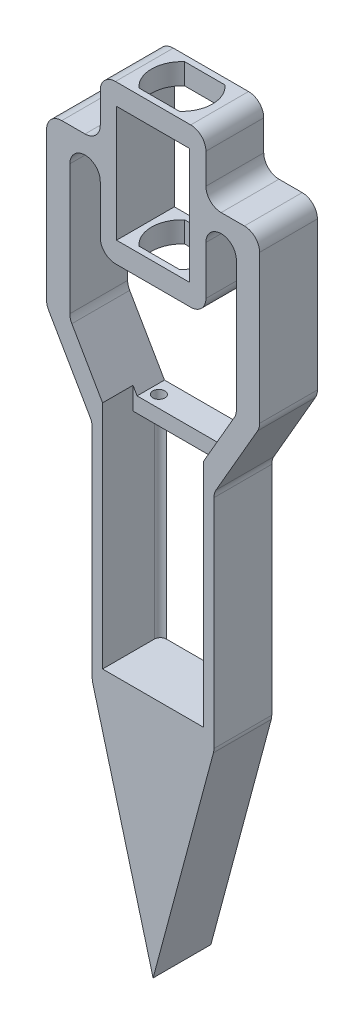
SolidWorks part; units mm, degrees
ref_plane "Front Plane" through (0, 0, 0) normal (0, 0, 1) x (1, 0, 0)
ref_plane "Top Plane" through (0, 0, 0) normal (0, 1, 0) x (1, 0, 0)
ref_plane "Right Plane" through (0, 0, 0) normal (1, 0, 0) x (0, 0, -1)
sketch "Sketch1" plane through (0, 0, 0) normal (0, 1, 0) x (1, 0, 0)
  line L0 (0, -7.5) -> (-6.64, -7.5)
  line L1 (-6.64, 7.5) -> (0, 7.5)
  line L2 (0, 7.5) -> (6.64, 7.5)
  line L3 (6.64, -7.5) -> (0, -7.5)
  line L4 (0.0497, 0) -> (-0.0497, 0) construction
  line L5 (0, -9.5) -> (-7.3633, -9.5)
  line L6 (-7.3633, 9.5) -> (0, 9.5)
  line L7 (0, 9.5) -> (7.3633, 9.5)
  line L8 (7.3633, -9.5) -> (0, -9.5)
  line L9 (0.0497, 2) -> (-0.0497, 2)
  arc A0 (-6.64, -7.5) -> (-6.64, 7.5) centre (0.0497, 0) cw
  arc A1 (6.64, 7.5) -> (6.64, -7.5) centre (-0.0497, 0) cw
  arc A2 (-7.3633, -9.5) -> (-7.3633, 9.5) centre (0.0497, 0) cw
  arc A3 (7.3633, 9.5) -> (7.3633, -9.5) centre (-0.0497, 0) cw
  point P8 (0, 0)
  dimension "D1" = 10.05
  dimension "D3" = 13.28
  dimension "D2" = 15
  dimension "D4" = 2
extrude "Boss-Extrude1" add sketch "Sketch1" along normal blind 6.9 contours A3 L7 L6 A2 L5 L8 L2 A1 L3 L0 A0 L1 region at (-3.6816, 0, 9.1939)
sketch "Sketch2" plane through (0, 6.9, 0) normal (0, 1, 0) x (1, 0, 0)
  line L0 (-7.3633, 9.5) -> (-17.3633, 9.5)
  line L1 (-17.3633, 9.5) -> (-17.3633, -9.5)
  line L2 (-17.3633, -9.5) -> (-7.3633, -9.5)
  arc A0 (-7.3633, 9.5) -> (-7.3633, -9.5) centre (0.0497, 0) ccw construction
  arc A1 (-7.3633, 9.5) -> (-7.3633, -9.5) centre (0.0497, 0) ccw
  dimension "D1" = 10
extrude "Boss-Extrude2" add sketch "Sketch2" against normal up to surface (6.9 mm away) and the other way blind 45 up to face at (0, 0, 0)
sketch "Sketch4" plane through (0, 6.9, 0) normal (0, 1, 0) x (1, 0, 0)
  line L0 (-10.9154, -4.9969) -> (-8.8633, -9.5)
  line L1 (-17.3633, -9.5) -> (-7.3633, -9.5) construction
  line L2 (-10.9154, 4.9969) -> (-8.8633, 9.5)
  line L3 (-7.3633, 9.5) -> (-17.3633, 9.5) construction
  line L4 (-8.8633, 9.5) -> (-7.3633, 9.5)
  line L5 (-7.3633, -9.5) -> (-8.8633, -9.5)
  arc A0 (-7.3633, 9.5) -> (-7.3633, -9.5) centre (0.0497, 0) ccw construction
  arc A1 (-7.3633, 9.5) -> (-10.9154, 4.9969) centre (0.0497, 0) ccw
  arc A2 (-10.9154, -4.9969) -> (-7.3633, -9.5) centre (0.0497, 0) ccw
  dimension "D1" = 1.5
  dimension "D2" = 1.5
extrude "Cut-Extrude1" cut sketch "Sketch4" along normal through all
mirror "Mirror2" about plane through (0, 0, 0) normal (1, 0, 0) of "Cut-Extrude1", "Boss-Extrude2"
ref_plane "Plane1" through (0, 19.9, 0) normal (0, 1, 0) x (1, 0, 0)
sketch "Sketch5" plane through (0, 19.9, 0) normal (0, 1, 0) x (1, 0, 0)
  line L6 (10.9154, 4.9969) -> (8.8633, 9.5)
  line L7 (8.8633, 9.5) -> (-8.8633, 9.5)
  line L8 (-8.8633, 9.5) -> (-10.9154, 4.9969)
  line L9 (-10.9154, -4.9969) -> (-8.8633, -9.5)
  line L10 (-8.8633, -9.5) -> (8.8633, -9.5)
  line L11 (8.8633, -9.5) -> (10.9154, -4.9969)
  line L12 (10.9154, 4.9969) -> (8.8633, 9.5)
  line L13 (8.8633, 9.5) -> (-8.8633, 9.5)
  line L14 (-8.8633, 9.5) -> (-10.9154, 4.9969)
  line L15 (-10.9154, -4.9969) -> (-8.8633, -9.5)
  line L16 (-8.8633, -9.5) -> (8.8633, -9.5)
  line L17 (8.8633, -9.5) -> (10.9154, -4.9969)
  circle A0 centre (0, 0) radius 5
  arc A4 (10.9154, -4.9969) -> (10.9154, 4.9969) centre (-0.0497, 0) ccw
  arc A5 (-10.9154, 4.9969) -> (-10.9154, -4.9969) centre (0.0497, 0) ccw
  arc A6 (10.9154, -4.9969) -> (10.9154, 4.9969) centre (-0.0497, 0) ccw
  arc A7 (-10.9154, 4.9969) -> (-10.9154, -4.9969) centre (0.0497, 0) ccw
  dimension "D1" = 10
  dimension "D2" = 0
extrude "Boss-Extrude3" [suppressed] add sketch "Sketch5" against normal blind 7.9
sketch "Sketch6" plane through (0, 51.9, 0) normal (0, 1, 0) x (1, 0, 0)
  line L0 (-6.64, 7.5) -> (6.64, 7.5) construction
  line L1 (6.64, -7.5) -> (-6.64, -7.5) construction
  line L2 (-6.64, 7.5) -> (6.64, 7.5)
  line L3 (6.64, -7.5) -> (-6.64, -7.5)
  line L6 (10.9154, 4.9969) -> (8.8633, 9.5)
  line L7 (8.8633, 9.5) -> (-8.8633, 9.5)
  line L8 (-8.8633, 9.5) -> (-10.9154, 4.9969)
  line L9 (-10.9154, -4.9969) -> (-8.8633, -9.5)
  line L10 (-8.8633, -9.5) -> (8.8633, -9.5)
  line L11 (8.8633, -9.5) -> (10.9154, -4.9969)
  line L12 (10.9154, 4.9969) -> (8.8633, 9.5)
  line L13 (8.8633, 9.5) -> (-8.8633, 9.5)
  line L14 (-8.8633, 9.5) -> (-10.9154, 4.9969)
  line L15 (-10.9154, -4.9969) -> (-8.8633, -9.5)
  line L16 (-8.8633, -9.5) -> (8.8633, -9.5)
  line L17 (8.8633, -9.5) -> (10.9154, -4.9969)
  arc A0 (6.64, -7.5) -> (6.64, 7.5) centre (-0.0497, 0) ccw construction
  arc A1 (-6.64, 7.5) -> (-6.64, -7.5) centre (0.0497, 0) ccw construction
  arc A2 (10.9154, -4.9969) -> (10.9154, 4.9969) centre (-0.0497, 0) ccw
  arc A3 (-10.9154, 4.9969) -> (-10.9154, -4.9969) centre (0.0497, 0) ccw
  arc A4 (10.9154, -4.9969) -> (10.9154, 4.9969) centre (-0.0497, 0) ccw
  arc A5 (-10.9154, 4.9969) -> (-10.9154, -4.9969) centre (0.0497, 0) ccw
  arc A6 (6.64, -7.5) -> (6.64, 7.5) centre (-0.0497, 0) ccw
  arc A7 (-6.64, 7.5) -> (-6.64, -7.5) centre (0.0497, 0) ccw
  dimension "D1" = 0
extrude "Boss-Extrude4" add sketch "Sketch6" against normal blind 6.9
sketch "Sketch7" plane through (0, 0, 9.5) normal (0, 0, 1) x (1, 0, 0)
  line L5 (-17.3633, 31.95) -> (-35, 31.95)
  line L6 (-17.3633, 51.9) -> (-17.3633, 0) construction
  line L7 (-35, 31.95) -> (-35, -23.05)
  line L8 (-35, -23.05) -> (-27.3633, -23.05)
  line L9 (-27.3633, -23.05) -> (-27.3633, 25.95)
  line L10 (-27.3633, 25.95) -> (-17.3633, 25.95)
  line L11 (-17.3633, 25.95) -> (-17.3633, 31.95)
  line L15 (17.3633, 0) -> (-17.3633, 0) construction
  point P12 (0, 0)
  dimension "D1" = 35
  dimension "D2" = 10
  dimension "D3" = 55
  dimension "D4" = 6
extrude "Boss-Extrude5" add sketch "Sketch7" against normal up to surface (19 mm away) up to face at (0, 25.95, -9.5)
mirror "Mirror4" about plane through (0, 0, 0) normal (1, 0, 0) of "Boss-Extrude5"
sketch "Sketch11" plane through (0, 0, 9.5) normal (0, 0, 1) x (1, 0, 0)
  line L0 (-35, -23.05) -> (-20, -49.0308)
  line L1 (-20, -49.0308) -> (20, -49.0308)
  line L2 (20, -49.0308) -> (35, -23.05)
  line L3 (35, -23.05) -> (27.3633, -23.05)
  line L4 (27.3633, -23.05) -> (15.25, -44.0308)
  line L5 (15.25, -44.0308) -> (-15.25, -44.0308)
  line L6 (-15.25, -44.0308) -> (-27.3633, -23.05)
  line L7 (-27.3633, -23.05) -> (-35, -23.05)
  point P3 (0, -44.0308)
  point P13 (0, -49.0308)
  dimension "D1" = 60
  dimension "D2" = 40
  dimension "D3" = 5
extrude "Boss-Extrude8" add sketch "Sketch11" against normal up to surface (19 mm away) up to face at (0, 25.95, -9.5)
sketch "Sketch15" plane through (0, 6.9, 0) normal (0, 1, 0) x (1, 0, 0)
  line L0 (-12.0003, 0) -> (-12.0003, 9.5)
  line L1 (-17.3633, 9.5) -> (17.3633, 9.5) construction
  line L2 (-12.0003, 9.5) -> (12.0003, 9.5)
  line L3 (12.0003, 9.5) -> (12.0003, 0)
  line L4 (-12.0003, 0) -> (-12.0003, -9.5)
  line L5 (17.3633, -9.5) -> (-17.3633, -9.5) construction
  line L6 (-12.0003, -9.5) -> (12.0003, -9.5)
  line L7 (12.0003, -9.5) -> (12.0003, 0)
  arc A0 (-10.9154, 4.9969) -> (-10.9154, -4.9969) centre (0.0497, 0) ccw construction
  arc A1 (10.9154, -4.9969) -> (10.9154, 4.9969) centre (-0.0497, 0) ccw construction
extrude "Cut-Extrude2" cut sketch "Sketch15" along normal up to surface (38.1 mm away) up to face at (0, 45, 0)
sketch "Sketch16" plane through (0, -49.0308, 0) normal (0, -1, 0) x (1, 0, 0)
  line L0 (-20, -9.5) -> (20, -9.5) construction
  line L1 (-20, 9.5) -> (-16.6, 9.5)
  line L2 (-20, 9.5) -> (-20, -9.5)
  line L3 (-20, -9.5) -> (-16.6, -9.5)
  line L4 (-16.6, 9.5) -> (-16.6, -9.5)
  line L5 (-20, 9.5) -> (20, 9.5) construction
  line L6 (20, -9.5) -> (16.6, -9.5)
  line L7 (20, -9.5) -> (20, 9.5)
  line L8 (20, 9.5) -> (16.6, 9.5)
  line L9 (16.6, -9.5) -> (16.6, 9.5)
  dimension "D1" = 3.4
  dimension "D2" = 3.4
extrude "Boss-Extrude10" add sketch "Sketch16" along normal blind 68.4
sketch "Sketch17" plane through (0, -49.0308, 0) normal (0, -1, 0) x (1, 0, 0)
  line L0 (-16.6, -9.5) -> (-16.6, 9.5) construction
  line L1 (-16.6, -9.5) -> (16.6, -9.5) construction
  line L2 (-14.6, -9.5) -> (-16.6, -9.5)
  line L3 (-16.6, -9.5) -> (-16.6, -7.5)
  line L4 (-16.6, -9.5) -> (-16.6, 9.5) construction
  line L5 (0, 0) -> (0, -9.5) construction
  line L6 (14.6, -9.5) -> (16.6, -9.5)
  line L7 (16.6, -9.5) -> (16.6, -7.5)
  arc A0 (-16.6, -7.5) -> (-14.6, -9.5) centre (-14.6, -7.5) ccw
  arc A1 (16.6, -7.5) -> (14.6, -9.5) centre (14.6, -7.5) cw
  dimension "D1" = 2
extrude "Boss-Extrude11" add sketch "Sketch17" along normal up to surface (68.4 mm away) up to face at (-18.3, -117.4308, 0)
sketch "Sketch18" plane through (0, -117.4308, 0) normal (0, -1, 0) x (1, 0, 0)
  line L1 (-20, -9.5) -> (20, -9.5)
  line L2 (-20, -9.5) -> (-20, 9.5)
  line L3 (-20, 9.5) -> (20, 9.5)
  line L4 (20, -9.5) -> (20, 9.5)
extrude "Boss-Extrude12" add sketch "Sketch18" along normal blind 5
sketch "Sketch20" plane through (0, -49.0308, 0) normal (0, -1, 0) x (1, 0, 0)
  line L0 (16.6, 9.5) -> (16.6, -7.5) construction
  line L1 (-16.6, 9.5) -> (16.6, 9.5)
  line L2 (-16.6, 9.5) -> (-16.6, -0.5)
  line L3 (-16.6, -0.5) -> (16.6, -0.5)
  line L4 (16.6, 9.5) -> (16.6, -0.5)
  dimension "D1" = 10
extrude "Cut-Extrude3" cut sketch "Sketch20" against normal up to surface (49.0308 mm away) up to face at (0, 0, 0)
sketch "Sketch21" plane through (0, 0, 9.5) normal (0, 0, 1) x (1, 0, 0)
  line L0 (-20, -122.4308) -> (0, -197.0718)
  line L1 (0, -197.0718) -> (20, -122.4308)
  line L2 (-20, -122.4308) -> (20, -122.4308)
  dimension "D1" = 30
extrude "Boss-Extrude13" add sketch "Sketch21" against normal up to surface (19 mm away) up to face at (0, -83.2308, -9.5)
fillet "Fillet1" radius 5 20 edges at (20, -122.4308, 0) (20, -49.0308, 0) (35, -23.05, 0) (35, 31.95, 0) (17.3633, 31.95, 0) (-17.3633, 31.95, 0) (-35, 31.95, 0) (-35, -23.05, 0) (-20, -49.0308, 0) (-20, -122.4308, 0) (-17.3633, 0, 0) (17.3633, 0, 0) (17.3633, 51.9, 0) (-17.3633, 51.9, 0) (-27.3633, -23.05, 0) (27.3633, -23.05, 0) (27.3633, 25.95, 0) (17.3633, 25.95, 0) (-27.3633, 25.95, 0) (-17.3633, 25.95, 0)
sketch "Sketch22" plane through (0, -49.0308, 0) normal (0, -1, 0) x (1, 0, 0)
  line L0 (-14.6, -9.5) -> (14.6, -9.5) construction
  line L1 (-16.6, -7.5) -> (-16.6, -0.5) construction
  circle A0 centre (-12.1, -4.5) radius 2
  dimension "D1" = 4
  dimension "D2" = 5
  dimension "D3" = 4.5
extrude "Cut-Extrude4" cut sketch "Sketch22" against normal up to surface (49.0308 mm away) up to face at (0, 0, 0)
